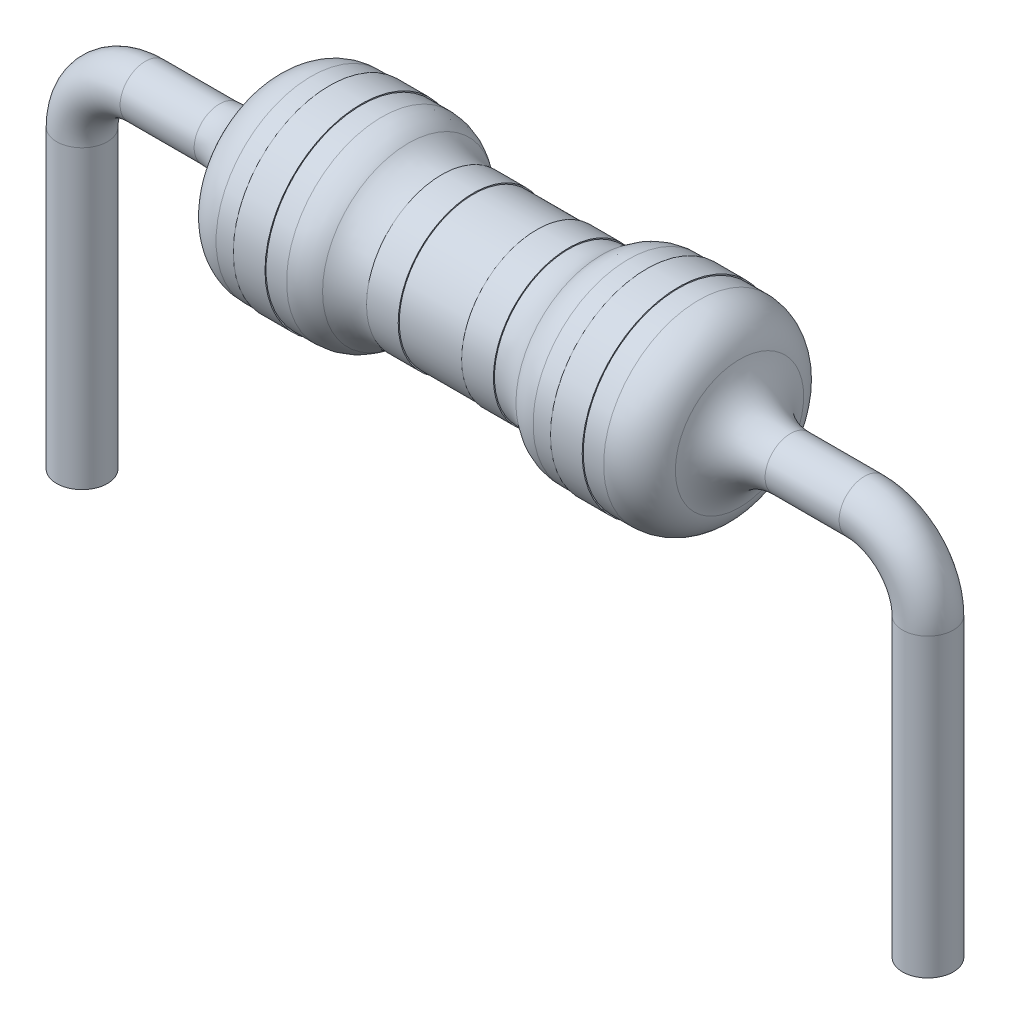
SolidWorks part; units mm, degrees
material "Nickel"
ref_plane "x/y" through (0, 0, 0) normal (0, 0, 1) x (1, 0, 0)
ref_plane "x/z" through (0, 0, 0) normal (0, 1, 0) x (1, 0, 0)
ref_plane "y/z" through (0, 0, 0) normal (1, 0, 0) x (0, 0, -1)
sketch "Sketch1" plane through (0, 0, 0) normal (0, 0, 1) x (1, 0, 0)
  line L0 (0, -2.54) -> (0, 1.016)
  line L1 (0.762, 1.778) -> (9.398, 1.778)
  line L2 (10.16, 1.016) -> (10.16, -2.54)
  arc A0 (0, 1.016) -> (0.762, 1.778) centre (0.762, 1.016) cw
  arc A1 (9.398, 1.778) -> (10.16, 1.016) centre (9.398, 1.016) cw
  dimension "D2" = 0.762
  dimension "D1" = 10.16
  dimension "D3" = 2.54
  dimension "D4" = 1.778
ref_plane "Plane4" through (0, -2.54, 0) normal (0, 1, 0) x (-1, 0, 0)
sketch "Sketch3" plane through (0, -2.54, 0) normal (0, 1, 0) x (-1, 0, 0)
  circle A0 centre (0, 0) radius 0.3048
  dimension "D1" = 0.6096
sweep "Base-Sweep" add profiles "Sketch3" path "Sketch1"
sketch "Sketch4" plane through (0, 0, 0) normal (0, 0, 1) x (1, 0, 0)
  line L0 (2.286, 2.0828) -> (2.286, 2.921)
  line L1 (9.398, 2.0828) -> (0.762, 2.0828) construction
  line L2 (2.286, 2.921) -> (3.81, 2.921)
  line L3 (3.81, 2.921) -> (3.81, 2.667)
  line L4 (3.81, 2.667) -> (6.35, 2.667)
  line L5 (6.35, 2.667) -> (6.35, 2.921)
  line L6 (6.35, 2.921) -> (7.874, 2.921)
  line L7 (7.874, 2.921) -> (7.874, 2.0828)
  line L8 (-3.217, 1.778) -> (13.0535, 1.778) construction
  line L12 (9.398, 2.0828) -> (0.762, 2.0828)
  line L13 (5.08, 2.0828) -> (5.08, 3.3524) construction
  point P12 (5.08, 2.667)
  dimension "D1" = 1.778
  dimension "D2" = 1.143
  dimension "D3" = 1.524
  dimension "D4" = 1.524
  dimension "D5" = 1.778
  dimension "D6" = 5.588
revolve "Revolve1" add sketch "Sketch4" angle 360 about L8 region at (5.08, 2.4552, 0)
fillet "Fillet5" radius 0.635 4 edges at (7.874, 1.778, -0.3048) (6.35, 1.778, 0.889) (3.81, 1.778, 0.889) (2.286, 1.778, 0.3048)
fillet "Fillet6" radius 0.508 4 edges at (7.874, 1.778, 1.143) (6.35, 1.778, 1.143) (3.81, 1.778, 1.143) (2.286, 1.778, 1.143)
ref_plane "Plane5" through (2.9718, 0, 0) normal (1, 0, 0) x (0, 0, -1)
sketch "Sketch5" plane through (2.9718, 0, 0) normal (1, 0, 0) x (0, 0, -1)
  circle A0 centre (0, 1.778) radius 1.143 construction
  circle A1 centre (0, 1.778) radius 1.143
extrude "Extrude-Thin1" add sketch "Sketch5" along normal blind 0.381 thin thin type one direction wall 0.0127
ref_plane "Plane6" through (4.318, 0, 0) normal (1, 0, 0) x (0, 0, -1)
sketch "Sketch6" plane through (4.318, 0, 0) normal (1, 0, 0) x (0, 0, -1)
  circle A0 centre (0, 1.778) radius 0.889 construction
  circle A1 centre (0, 1.778) radius 0.889
extrude "Extrude-Thin2" add sketch "Sketch6" along normal blind 0.381 thin thin type one direction wall 0.0127
ref_plane "Plane7" through (5.461, 0, 0) normal (1, 0, 0) x (0, 0, -1)
sketch "Sketch7" plane through (5.461, 0, 0) normal (1, 0, 0) x (0, 0, -1)
  circle A0 centre (0, 1.778) radius 0.889 construction
  circle A1 centre (0, 1.778) radius 0.889
extrude "Extrude-Thin3" add sketch "Sketch7" along normal blind 0.381 thin thin type one direction wall 0.0127
ref_plane "Plane8" through (6.7818, 0, 0) normal (1, 0, 0) x (0, 0, -1)
sketch "Sketch8" plane through (6.7818, 0, 0) normal (1, 0, 0) x (0, 0, -1)
  circle A0 centre (0, 1.778) radius 1.143 construction
  circle A1 centre (0, 1.778) radius 1.143
extrude "Extrude-Thin4" add sketch "Sketch8" along normal blind 0.381 thin thin type one direction wall 0.0127
